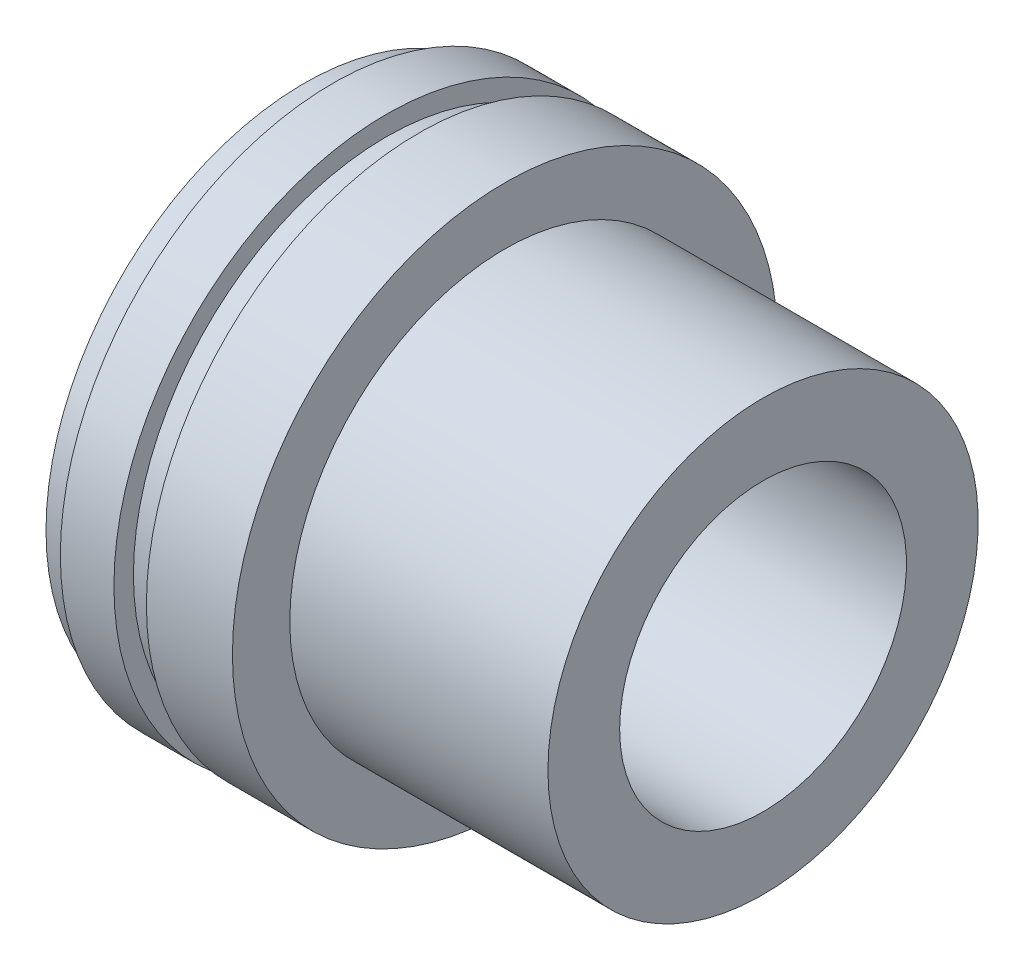
SolidWorks part; units mm, degrees
material "Epoxy, Unfilled"
ref_plane "Front Plane" through (0, 0, 0) normal (0, 0, 1) x (1, 0, 0)
ref_plane "Top Plane" through (0, 0, 0) normal (0, 1, 0) x (1, 0, 0)
ref_plane "Right Plane" through (0, 0, 0) normal (1, 0, 0) x (0, 0, -1)
sketch "Sketch1" plane through (0, 0, 0) normal (0, 0, 1) x (1, 0, 0)
  line L0 (0, 0) -> (0, 9.525)
  line L2 (0, 9.525) -> (25.4, 9.525)
  line L4 (25.4, 9.525) -> (44.45, 28.575)
  line L5 (44.45, 0) -> (44.45, 12.7)
  line L6 (44.45, 28.575) -> (101.6, 28.575)
  line L9 (44.45, 12.7) -> (101.6, 12.7)
  line L10 (101.6, 12.7) -> (101.6, 28.575)
  line L11 (0, 0) -> (18.2118, 0)
  line L12 (0, 60.325) -> (98.3752, 60.325) construction
  line L13 (44.45, 0) -> (25.4, 0)
  line L14 (25.4, 0) -> (25.4, 4.318)
  line L15 (25.4, 4.318) -> (18.2118, 4.318)
  line L16 (18.2118, 4.318) -> (18.2118, 0)
  line L17 (0, 0) -> (6.35, 0)
  line L18 (6.35, 0) -> (6.35, 3.175)
  line L19 (6.35, 3.175) -> (0, 3.175)
  dimension "D1" = 57.15
  dimension "D2" = 25.4
  dimension "D3" = 60.325
  dimension "D4" = 9.525
  dimension "D5" = 19.05
  dimension "D6" = 45
  dimension "D7" = 57.15
  dimension "D8" = 44.45
  dimension "D9" = 12.7
  dimension "D10" = 4.318
  dimension "D11" = 7.1882
  dimension "D12" = 19.05
revolve "Revolve1" add sketch "Sketch1" angle 360 about L12 region at (56.0168, 16.1007, 0)
